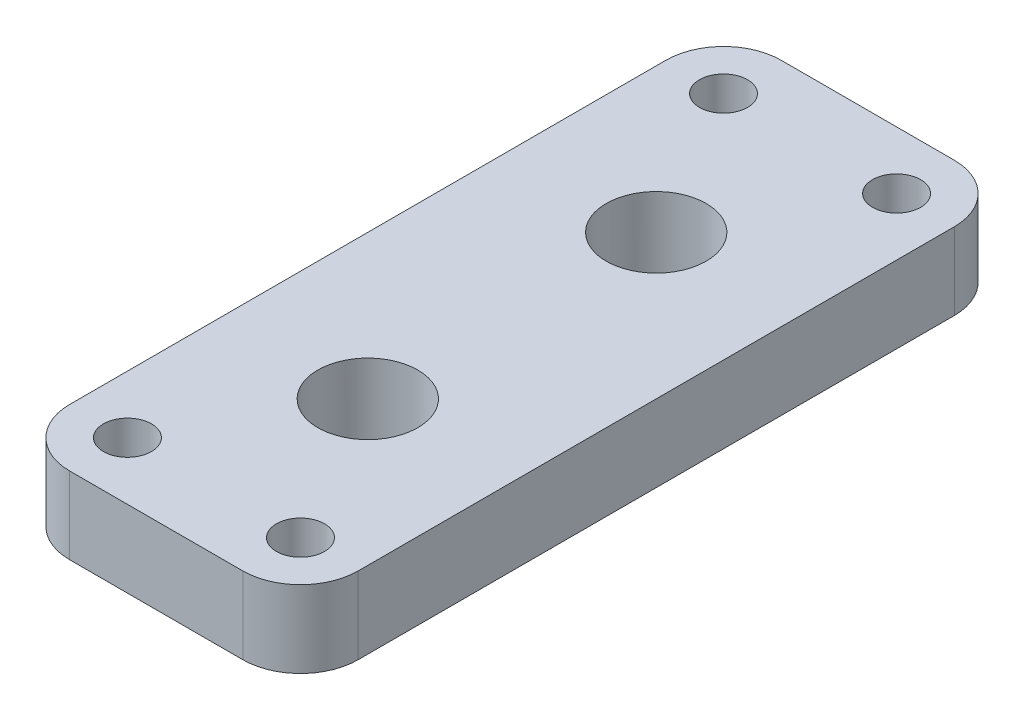
SolidWorks part; units mm, degrees
ref_plane "前视基准面" through (0, 0, 0) normal (0, 0, 1) x (1, 0, 0)
ref_plane "上视基准面" through (0, 0, 0) normal (0, 1, 0) x (1, 0, 0)
ref_plane "右视基准面" through (0, 0, 0) normal (1, 0, 0) x (0, 0, -1)
other "Configuration Table"
sketch "草图1" plane through (0, 0, 0) normal (0, 1, 0) x (1, 0, 0)
  line L1 (-32.5, 12.5) -> (32.5, 12.5)
  line L2 (-32.5, 12.5) -> (-32.5, -12.5)
  line L3 (-32.5, -12.5) -> (32.5, -12.5)
  line L4 (32.5, 12.5) -> (32.5, -12.5)
  line L5 (0, -12.5) -> (0, 12.5) construction
  line L6 (-32.5, 0) -> (32.5, 0) construction
  point P0 (0, 0)
  dimension "D1" = 25
  dimension "D2" = 65
extrude "凸台-拉伸1" add sketch "草图1" along normal blind 4
sketch "草图2" plane through (0, 4, 0) normal (0, 1, 0) x (1, 0, 0)
  line L0 (-32.5, -12.5) -> (32.5, -12.5) construction
  line L1 (-7.5, 12.5) -> (7.5, 12.5)
  line L2 (-7.5, 12.5) -> (-7.5, -12.5)
  line L3 (-7.5, -12.5) -> (7.5, -12.5)
  line L4 (7.5, 12.5) -> (7.5, -12.5)
  line L5 (0, -12.5) -> (0, 12.5) construction
  line L6 (-7.5, 0) -> (7.5, 0) construction
  point P0 (0, 0)
  dimension "D1" = 15
extrude "凸台-拉伸2" add sketch "草图2" along normal blind 13
sketch "草图3" plane through (0, 0, 0) normal (0, -1, 0) x (1, 0, 0)
  line L0 (0, 12.5) -> (0, -12.5) construction
  line L1 (-32.5, 12.5) -> (32.5, 12.5) construction
  line L2 (32.5, -12.5) -> (-32.5, -12.5) construction
  line L3 (-32.5, 0) -> (32.5, 0) construction
  line L4 (-32.5, -12.5) -> (-32.5, 12.5) construction
  line L5 (32.5, 12.5) -> (32.5, -12.5) construction
  circle A0 centre (0, -7.5) radius 2.6
  circle A1 centre (0, 7.5) radius 2.6
  circle A2 centre (-22, 0) radius 4.1
  circle A3 centre (22, 0) radius 4.1
  dimension "D1" = 5.2
  dimension "D3" = 8.2
  dimension "D2" = 5
  dimension "D4" = 22
extrude "切除-拉伸1" cut sketch "草图3" against normal through all
sketch "草图5" plane through (0, 0, 12.5) normal (0, 0, 1) x (1, 0, 0)
  line L0 (7.5, 17) -> (7.5, 4) construction
  line L1 (-7.5, 4) -> (7.5, 4)
  line L2 (-7.5, 4) -> (-7.5, 8)
  line L3 (-7.5, 8) -> (7.5, 8)
  line L4 (7.5, 4) -> (7.5, 8)
  dimension "D1" = 4
extrude "凸台-拉伸3" add sketch "草图5" along normal blind 6
sketch "草图6" plane through (0, 4, 0) normal (0, -1, 0) x (1, 0, 0)
  line L0 (0, 18.5) -> (0, 12.5) construction
  line L1 (-7.5, 18.5) -> (7.5, 18.5) construction
  line L2 (-32.5, 12.5) -> (32.5, 12.5) construction
  line L3 (-7.5, 18.5) -> (-7.5, 12.5) construction
  circle A0 centre (-4.5, 15.5) radius 1.25
  circle A1 centre (4.5, 15.5) radius 1.25
  point P11 (-7.5, 15.5)
  dimension "D1" = 2.5
  dimension "D2" = 3
extrude "切除-拉伸3" cut sketch "草图6" against normal through all
ref_plane "基准面2" through (0, 0, 0) normal (0, 0, 1) x (1, 0, 0)
mirror "镜向2" about plane through (0, 0, 0) normal (0, 0, 1) of "凸台-拉伸3", "切除-拉伸3"
fillet "圆角2" radius 3 4 edges at (-7.5, 6, -18.5) (7.5, 6, -18.5) (-7.5, 6, 18.5) (7.5, 6, 18.5)
sketch "草图7" plane through (0, 0, -12.5) normal (0, 0, -1) x (-1, 0, 0)
  line L6 (32.5, 4) -> (7.5, 4)
  line L7 (7.5, 4) -> (-7.5, 4)
  line L8 (-7.5, 4) -> (-32.5, 4)
  line L9 (-32.5, 4) -> (-32.5, 0)
  line L10 (-32.5, 0) -> (32.5, 0)
  line L11 (32.5, 0) -> (32.5, 4)
  line L12 (32.5, 4) -> (7.5, 4)
  line L13 (7.5, 4) -> (-7.5, 4)
  line L14 (-7.5, 4) -> (-32.5, 4)
  line L15 (-32.5, 4) -> (-32.5, 0)
  line L16 (-32.5, 0) -> (32.5, 0)
  line L17 (32.5, 0) -> (32.5, 4)
  dimension "D1" = 0
extrude "切除-拉伸4" cut sketch "草图7" against normal through all
sketch "草图8" plane through (0, 0, 12.5) normal (0, 0, 1) x (1, 0, 0)
  line L1 (-7.5, 8) -> (7.5, 8)
  line L2 (-7.5, 8) -> (-7.5, 17)
  line L3 (-7.5, 17) -> (7.5, 17)
  line L4 (7.5, 8) -> (7.5, 17)
extrude "切除-拉伸5" cut sketch "草图8" against normal through all
